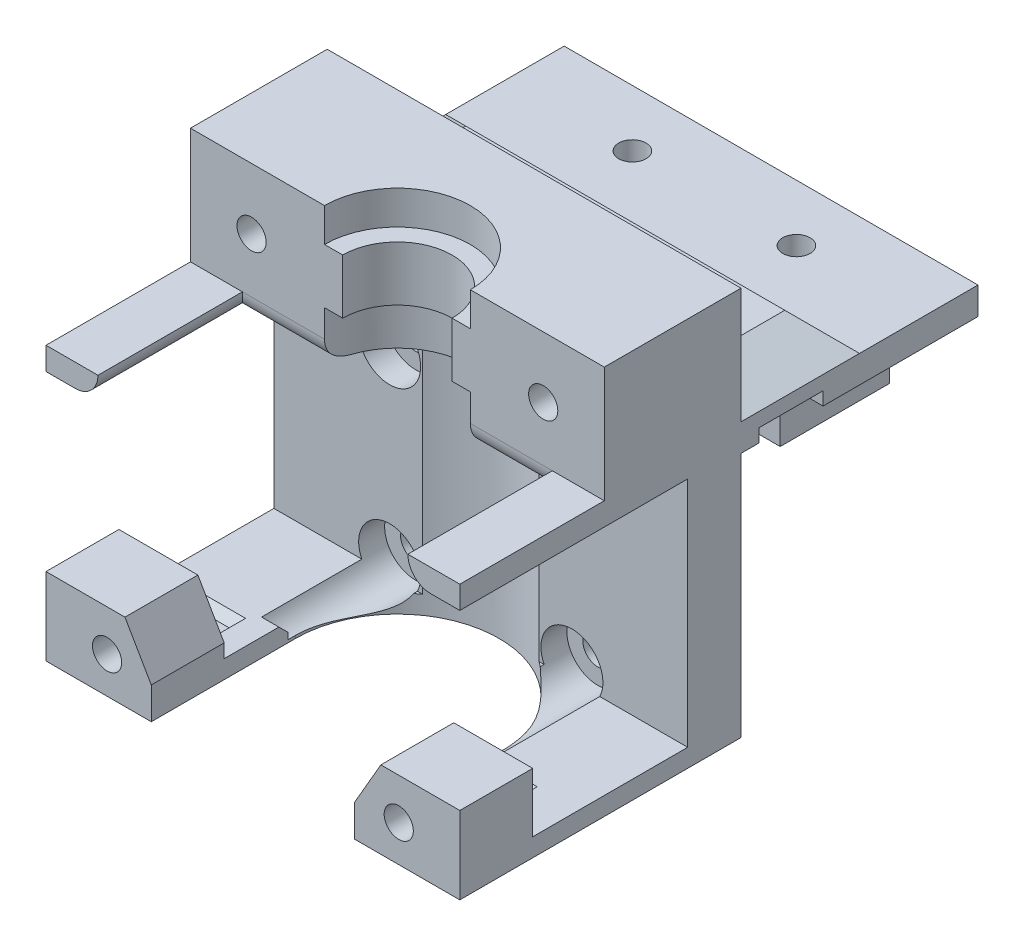
SolidWorks part; units mm, degrees
ref_plane "Front Plane" through (0, 0, 0) normal (0, 0, 1) x (1, 0, 0)
ref_plane "Top Plane" through (0, 0, 0) normal (0, 1, 0) x (1, 0, 0)
ref_plane "Right Plane" through (0, 0, 0) normal (1, 0, 0) x (0, 0, -1)
sketch "Sketch1" plane through (0, 0, 0) normal (0, 0, 1) x (1, 0, 0)
  line L1 (0, 0) -> (45.4, 0)
  line L2 (0, 0) -> (0, 27)
  line L3 (0, 27) -> (45.4, 27)
  line L4 (45.4, 0) -> (45.4, 27)
  dimension "D1" = 45.4
  dimension "D2" = 27
extrude "Boss-Extrude1" add sketch "Sketch1" along normal blind 5.85
sketch "Sketch3" plane through (0, 27, 0) normal (0, 1, 0) x (1, 0, 0)
  line L0 (45.4, 0) -> (0, 0) construction
  line L1 (45.4, 0) -> (0, 0)
  line L2 (45.4, 0) -> (45.4, -5.85)
  line L3 (45.4, -5.85) -> (0, -5.85)
  line L4 (0, 0) -> (0, -5.85)
  line L5 (45.4, -5.85) -> (45.4, 0) construction
  line L6 (45.4, -5.85) -> (0, -5.85) construction
extrude "Boss-Extrude2" add sketch "Sketch3" along normal blind 3
sketch "Sketch4" plane through (0, 0, 5.85) normal (0, 0, 1) x (1, 0, 0)
  line L0 (0, 30) -> (45.4, 30) construction
  line L1 (45.4, 30) -> (0, 30)
  line L2 (45.4, 30) -> (45.4, 27.5)
  line L3 (45.4, 27.5) -> (0, 27.5)
  line L4 (0, 30) -> (0, 27.5)
  line L5 (45.4, 0) -> (45.4, 30) construction
  line L6 (0, 30) -> (0, 0) construction
  dimension "D1" = 2.5
extrude "Boss-Extrude3" add sketch "Sketch4" along normal blind 25
sketch "Sketch6" plane through (0, 0, 5.85) normal (0, 0, 1) x (1, 0, 0)
  line L0 (45.4, 0) -> (45.4, 27.5) construction
  line L1 (0, 0) -> (45.4, 0)
  line L2 (0, 0) -> (0, 2)
  line L3 (0, 2) -> (45.4, 2)
  line L4 (45.4, 0) -> (45.4, 2)
  dimension "D1" = 2
extrude "Boss-Extrude5" add sketch "Sketch6" along normal up to surface (25 mm away) up to face at (22.7, 28.75, 30.85)
sketch "Sketch7" plane through (0, 0, 5.85) normal (0, 0, 1) x (1, 0, 0)
  line L1 (12.7, 23.5) -> (32.7, 23.5) construction
  line L2 (12.7, 23.5) -> (12.7, 3.5) construction
  line L3 (12.7, 3.5) -> (32.7, 3.5) construction
  line L4 (32.7, 23.5) -> (32.7, 3.5) construction
  line L5 (12.7, 23.5) -> (32.7, 3.5) construction
  line L6 (12.7, 3.5) -> (32.7, 23.5) construction
  line L9 (22.7, 2) -> (22.7, 27.5) construction
  line L10 (45.4, 2) -> (0, 2) construction
  line L11 (0, 27.5) -> (45.4, 27.5) construction
  circle A0 centre (12.7, 23.5) radius 1.65
  circle A1 centre (32.7, 23.5) radius 1.65
  circle A2 centre (32.7, 3.5) radius 1.65
  circle A3 centre (12.7, 3.5) radius 1.65
  point P5 (22.7, 13.5)
  dimension "D3" = 3.3
  dimension "D1" = 20
  dimension "D2" = 20
  dimension "D4" = 13.5
extrude "Cut-Extrude1" cut sketch "Sketch7" against normal blind 10
sketch "Sketch8" plane through (0, 0, 5.85) normal (0, 0, 1) x (1, 0, 0)
  circle A0 centre (12.7, 23.5) radius 3.4
  circle A1 centre (32.7, 23.5) radius 3.4
  circle A2 centre (32.7, 3.5) radius 3.4
  circle A3 centre (12.7, 3.5) radius 3.4
  dimension "D1" = 6.8
extrude "Cut-Extrude2" cut sketch "Sketch8" against normal offset from surface 3 and the other way blind 10 up to face at (11.05, 3.5, 0)
sketch "Sketch37" plane through (0, 30, 0) normal (0, 1, 0) x (1, 0, 0)
  line L0 (45.4, 0) -> (0, 0) construction
  line L1 (45.4, -15) -> (0, -15)
  line L2 (45.4, -15) -> (45.4, 0)
  line L3 (45.4, 0) -> (0, 0)
  line L4 (0, -15) -> (0, 0)
  line L5 (22.7, 0) -> (22.7, -15) construction
  line L6 (45.4, 0) -> (0, 0) construction
  line L7 (0, 0) -> (0, -30.85) construction
  dimension "D2" = 15
extrude "Boss-Extrude16" add sketch "Sketch37" along normal blind 12.7
sketch "Sketch9" plane through (0, 2, 0) normal (0, 1, 0) x (1, 0, 0)
  line L1 (22.7, -5.85) -> (22.7, -30.85) construction
  line L3 (0, -30.85) -> (45.4, -30.85) construction
  line L6 (11.55, -15) -> (11.55, -30.85)
  line L7 (11.55, -30.85) -> (33.85, -30.85)
  line L8 (33.85, -15) -> (33.85, -30.85)
  line L9 (11.55, -15) -> (33.85, -30.85) construction
  line L10 (11.55, -30.85) -> (33.85, -15) construction
  arc A1 (33.85, -15) -> (11.55, -15) centre (22.7, -15) ccw
  point P13 (22.7, -22.925)
  dimension "D1" = 11.15
  dimension "D2" = 22.3
extrude "Cut-Extrude3" cut sketch "Sketch9" against normal through all
sketch "Sketch10" plane through (0, 27.5, 0) normal (0, -1, 0) x (1, 0, 0)
  line L1 (14.7, 15) -> (14.7, 30.85)
  line L2 (30.7, 15) -> (30.7, 30.85)
  line L3 (14.7, 30.85) -> (30.7, 30.85)
  line L4 (0, 30.85) -> (45.4, 30.85) construction
  arc A0 (14.7, 15) -> (30.7, 15) centre (22.7, 15) ccw
  dimension "D1" = 16
extrude "Cut-Extrude4" cut sketch "Sketch10" against normal through all
ref_plane "Plane2" through (0, 33, 0) normal (0, 1, 0) x (1, 0, 0)
sketch "Sketch18" plane through (0, 0, 0) normal (0, 0, -1) x (-1, 0, 0)
  line L0 (-45.4, 0) -> (-45.4, 42.7) construction
  line L1 (0, 27) -> (-45.4, 27)
  line L2 (0, 27) -> (0, 30)
  line L3 (0, 30) -> (-45.4, 30)
  line L4 (-45.4, 27) -> (-45.4, 30)
  line L5 (0, 27) -> (-45.4, 30) construction
  line L6 (0, 30) -> (-45.4, 27) construction
  line L7 (0, 42.7) -> (0, 0) construction
  line L11 (0, 0) -> (-45.4, 0) construction
  point P4 (-22.7, 28.5)
  dimension "D1" = 3
  dimension "D2" = 27
extrude "Boss-Extrude8" add sketch "Sketch18" along normal blind 26
sketch "Sketch19" plane through (0, 27, 0) normal (0, -1, 0) x (1, 0, 0)
  line L0 (45.4, -26) -> (0, -26) construction
  line L1 (35.7, -26) -> (9.7, -26)
  line L2 (35.7, -26) -> (35.7, -14)
  line L3 (35.7, -14) -> (9.7, -14)
  line L4 (9.7, -26) -> (9.7, -14)
  line L5 (35.7, -26) -> (9.7, -14) construction
  line L6 (35.7, -14) -> (9.7, -26) construction
  line L7 (22.7, -26) -> (22.7, 0) construction
  line L8 (45.4, -26) -> (0, -26) construction
  line L9 (0, 0) -> (45.4, 0) construction
  point P4 (22.7, -20)
  dimension "D1" = 12
  dimension "D2" = 26
extrude "Boss-Extrude9" add sketch "Sketch19" along normal blind 11.2
sketch "Sketch20" plane through (0, 15.8, 0) normal (0, -1, 0) x (1, 0, 0)
  line L0 (9.7, -26) -> (0, -26) construction
  line L1 (31.698, -19.7827) -> (13.6999, -19.7827) construction
  circle A0 centre (31.698, -19.7827) radius 1.5
  circle A1 centre (13.6999, -19.7827) radius 1.5
  dimension "D1" = 3
  dimension "D2" = 3
  dimension "D3" = 17.9981
  dimension "D5" = 6.2173
extrude "Cut-Extrude9" cut sketch "Sketch20" against normal through all
sketch "Sketch21" plane through (0, 30, 0) normal (0, 1, 0) x (1, 0, 0)
  line L1 (45.4, 0) -> (0, 0)
  line L2 (45.4, 0) -> (45.4, 10)
  line L3 (45.4, 10) -> (0, 10)
  line L4 (0, 0) -> (0, 10)
  line L5 (45.4, 0) -> (0, 10) construction
  line L6 (45.4, 10) -> (0, 0) construction
  line L7 (0, 26) -> (0, 0) construction
  line L8 (45.4, -30.85) -> (45.4, -15) construction
  point P4 (22.7, 5)
  dimension "D1" = 10
extrude "Boss-Extrude10" add sketch "Sketch21" along normal blind 3
sketch "Sketch22" plane through (45.4, 0, 0) normal (1, 0, 0) x (0, 0, -1)
  line L0 (26, 27) -> (0, 27) construction
  line L1 (2, 27) -> (9, 27)
  line L2 (2, 27) -> (2, 28.45)
  line L3 (2, 28.45) -> (9, 28.45)
  line L4 (9, 27) -> (9, 28.45)
  line L5 (2, 27) -> (9, 28.45) construction
  line L6 (2, 28.45) -> (9, 27) construction
  line L8 (0, 0) -> (0, 27) construction
  point P4 (5.5, 27.725)
  dimension "D1" = 1.45
  dimension "D2" = 2
  dimension "D3" = 7
extrude "Cut-Extrude10" cut sketch "Sketch22" against normal through all
sketch "Sketch23" plane through (0, 28.45, 0) normal (0, -1, 0) x (1, 0, 0)
  line L0 (0, -9) -> (45.4, -9) construction
  line L1 (10, -9) -> (13, -9)
  line L2 (10, -9) -> (10, -2)
  line L3 (10, -2) -> (13, -2)
  line L4 (13, -9) -> (13, -2)
  line L5 (10, -9) -> (13, -2) construction
  line L6 (10, -2) -> (13, -9) construction
  line L7 (0, -2) -> (45.4, -2) construction
  line L9 (32.4, -9) -> (35.4, -9)
  line L10 (32.4, -9) -> (32.4, -2)
  line L11 (32.4, -2) -> (35.4, -2)
  line L12 (35.4, -9) -> (35.4, -2)
  line L13 (32.4, -9) -> (35.4, -2) construction
  line L14 (32.4, -2) -> (35.4, -9) construction
  line L15 (0, -9) -> (0, -2) construction
  line L16 (45.4, -9) -> (45.4, -2) construction
  point P4 (11.5, -5.5)
  point P13 (33.9, -5.5)
  dimension "D1" = 3
  dimension "D2" = 3
  dimension "D3" = 10
  dimension "D4" = 10
extrude "Cut-Extrude11" cut sketch "Sketch23" against normal blind 10
sketch "Sketch24" plane through (0, 28.45, 0) normal (0, -1, 0) x (1, 0, 0)
  line L1 (13, -2) -> (32.4, -2)
  line L2 (13, -2) -> (13, -9)
  line L3 (13, -9) -> (32.4, -9)
  line L4 (32.4, -2) -> (32.4, -9)
  line L5 (13, -2) -> (32.4, -9) construction
  line L6 (13, -9) -> (32.4, -2) construction
  point P4 (22.7, -5.5)
extrude "Boss-Extrude11" add sketch "Sketch24" along normal up to surface (1.45 mm away) up to face at (22.7, 27, -18.75)
chamfer "Chamfer1" distance 8 angle 45 2 edges at (32.4, 33, -5.5) (13, 33, -5.5)
chamfer "Chamfer2" distance 3 angle 60 2 edges at (45.4, 33, -5) (0, 33, -5)
chamfer "Chamfer3" distance 3 angle 45 1 edges at (22.7, 30, -10)
chamfer "Chamfer4" distance 2.1 angle 45 2 edges at (9.7, 27, -20) (35.7, 27, -20)
sketch "Sketch35" plane through (0, 0, -26) normal (0, 0, -1) x (-1, 0, 0)
  line L0 (0, 27) -> (0, 30) construction
  line L1 (0, 27) -> (-7.6, 27)
  line L2 (0, 27) -> (0, 28.5)
  line L3 (0, 28.5) -> (-7.6, 28.5)
  line L4 (-7.6, 27) -> (-7.6, 28.5)
  line L5 (0, 27) -> (-7.6, 28.5) construction
  line L6 (0, 28.5) -> (-7.6, 27) construction
  point P4 (-3.8, 27.75)
  point P9 (-7.6, 27)
  dimension "D1" = 1.5
extrude "Cut-Extrude14" cut sketch "Sketch35" against normal up to surface (12 mm away) up to face at (22.7, 22.5667, -14)
fillet "Fillet8" radius 10 1 edges at (7.6, 28.5, -20)
sketch "Sketch36" plane through (0, 27.5, 0) normal (0, -1, 0) x (1, 0, 0)
  circle A0 centre (22.7, 15) radius 11.15
extrude "Cut-Extrude15" cut sketch "Sketch36" along normal up to surface (25.5 mm away) up to face at (7.0663, 2, 17.5167)
sketch "Sketch39" plane through (0, 33, 0) normal (0, 1, 0) x (1, 0, 0)
  circle A0 centre (22.7, -15) radius 8
  circle A1 centre (22.7, -15) radius 6
extrude "Boss-Extrude17" add sketch "Sketch39" along normal blind 6
sketch "Sketch40" plane through (0, 30, 0) normal (0, 1, 0) x (1, 0, 0)
  line L1 (0, -15) -> (45.4, -15)
  line L2 (0, -15) -> (0, -25)
  line L3 (0, -25) -> (45.4, -25)
  line L4 (45.4, -15) -> (45.4, -25)
  line L5 (0, -15) -> (45.4, -25) construction
  line L6 (0, -25) -> (45.4, -15) construction
  line L7 (45.4, -15) -> (45.4, 0) construction
  line L8 (0, -15) -> (14.7, -15) construction
  line L9 (0, 0) -> (0, -15) construction
  point P4 (22.7, -20)
  dimension "D1" = 10
extrude "Cut-Extrude16" cut sketch "Sketch40" along normal through all
sketch "Sketch41" plane through (0, 0, 15) normal (0, 0, 1) x (1, 0, 0)
  line L0 (30.7, 42.7) -> (45.4, 42.7) construction
  line L2 (0, 42.7) -> (0, 30) construction
  line L3 (45.4, 42.7) -> (45.4, 30) construction
  line L4 (0, 42.7) -> (14.7, 42.7) construction
  circle A0 centre (6.7, 36) radius 1.6
  circle A1 centre (38.7, 36) radius 1.6
  dimension "D1" = 3.2
  dimension "D2" = 3.2
  dimension "D3" = 6.7
  dimension "D4" = 6.7
  dimension "D5" = 6.7
  dimension "D6" = 6.7
extrude "Cut-Extrude17" cut sketch "Sketch41" against normal through all
sketch "Sketch42" plane through (0, 0, 0) normal (0, 0, -1) x (-1, 0, 0)
  line L1 (-40.3743, 38.9) -> (-42.0486, 36)
  line L2 (-42.0486, 36) -> (-40.3743, 33.1)
  line L3 (-40.3743, 33.1) -> (-37.0257, 33.1)
  line L4 (-37.0257, 33.1) -> (-35.3514, 36)
  line L5 (-35.3514, 36) -> (-37.0257, 38.9)
  line L6 (-37.0257, 38.9) -> (-40.3743, 38.9)
  line L7 (-8.3743, 38.9) -> (-10.0486, 36)
  line L8 (-10.0486, 36) -> (-8.3743, 33.1)
  line L9 (-8.3743, 33.1) -> (-5.0257, 33.1)
  line L10 (-5.0257, 33.1) -> (-3.3514, 36)
  line L11 (-3.3514, 36) -> (-5.0257, 38.9)
  line L12 (-5.0257, 38.9) -> (-8.3743, 38.9)
  line L14 (-45.4, 42.7) -> (0, 42.7) construction
  circle A0 centre (-38.7, 36) radius 2.9 construction
  circle A1 centre (-6.7, 36) radius 2.9 construction
  dimension "D1" = 5.8
extrude "Cut-Extrude18" cut sketch "Sketch42" against normal blind 4 and the other way blind 18
sketch "Sketch43" plane through (0, 0, 30.85) normal (0, 0, 1) x (1, 0, 0)
  line L1 (0, 2) -> (11.55, 2)
  line L2 (0, 2) -> (0, 8.5)
  line L3 (0, 8.5) -> (11.55, 8.5)
  line L4 (11.55, 2) -> (11.55, 8.5)
  line L5 (0, 2) -> (11.55, 8.5) construction
  line L6 (0, 8.5) -> (11.55, 2) construction
  line L7 (45.4, 2) -> (33.85, 2)
  line L8 (45.4, 2) -> (45.4, 8.5)
  line L9 (45.4, 8.5) -> (33.85, 8.5)
  line L10 (33.85, 2) -> (33.85, 8.5)
  line L11 (45.4, 2) -> (33.85, 8.5) construction
  line L12 (45.4, 8.5) -> (33.85, 2) construction
  point P4 (5.775, 5.25)
  point P10 (39.625, 5.25)
  point P12 (11.55, 2)
  point P14 (33.85, 2)
  dimension "D2" = 6.5
  dimension "D4" = 6.5
extrude "Boss-Extrude18" add sketch "Sketch43" against normal blind 8
sketch "Sketch44" plane through (0, 0, 30.85) normal (0, 0, 1) x (1, 0, 0)
  line L1 (0, 0) -> (0, 8.5) construction
  line L2 (45.4, 8.5) -> (45.4, 0) construction
  line L4 (11.55, 0) -> (0, 0) construction
  line L5 (45.4, 0) -> (33.85, 0) construction
  circle A0 centre (6.7, 4) radius 1.6
  circle A1 centre (38.7, 4) radius 1.6
  dimension "D1" = 3.2
  dimension "D2" = 4
  dimension "D3" = 6.7
  dimension "D4" = 6.7
  dimension "D5" = 4
extrude "Cut-Extrude19" cut sketch "Sketch44" against normal blind 10
sketch "Sketch45" plane through (0, 0, 22.85) normal (0, 0, -1) x (-1, 0, 0)
  line L0 (-45.4, 8.5) -> (-33.85, 8.5) construction
  line L1 (-40.3743, 6.9) -> (-42.0486, 4)
  line L2 (-42.0486, 4) -> (-40.3743, 1.1)
  line L3 (-40.3743, 1.1) -> (-37.0257, 1.1)
  line L4 (-37.0257, 1.1) -> (-35.3514, 4)
  line L5 (-35.3514, 4) -> (-37.0257, 6.9)
  line L6 (-37.0257, 6.9) -> (-40.3743, 6.9)
  line L7 (-8.3743, 6.9) -> (-10.0486, 4)
  line L8 (-10.0486, 4) -> (-8.3743, 1.1)
  line L9 (-8.3743, 1.1) -> (-5.0257, 1.1)
  line L10 (-5.0257, 1.1) -> (-3.3514, 4)
  line L11 (-3.3514, 4) -> (-5.0257, 6.9)
  line L12 (-5.0257, 6.9) -> (-8.3743, 6.9)
  line L13 (-11.55, 8.5) -> (0, 8.5) construction
  circle A0 centre (-38.7, 4) radius 2.9 construction
  circle A1 centre (-6.7, 4) radius 2.9 construction
  dimension "D1" = 5.8
extrude "Cut-Extrude20" cut sketch "Sketch45" against normal blind 4 and the other way blind 4
sketch "Sketch46" plane through (0, 0, 22.85) normal (0, 0, -1) x (-1, 0, 0)
  line L0 (-36.7368, 8.5) -> (-33.85, 3.5)
  line L1 (-45.4, 8.5) -> (-33.85, 8.5) construction
  line L2 (-33.85, 8.5) -> (-33.85, 2) construction
  line L3 (-33.85, 3.5) -> (-33.85, 8.5)
  line L4 (-33.85, 8.5) -> (-36.7368, 8.5)
  line L5 (-35.3514, 4) -> (-37.0257, 6.9) construction
  line L6 (-11.55, 8.5) -> (-8.6632, 8.5)
  line L7 (-11.55, 8.5) -> (0, 8.5) construction
  line L8 (-8.6632, 8.5) -> (-11.55, 3.5)
  line L9 (-11.55, 2) -> (-11.55, 8.5) construction
  line L10 (-11.55, 3.5) -> (-11.55, 8.5)
  line L11 (-8.3743, 6.9) -> (-10.0486, 4) construction
  dimension "D1" = 5
  dimension "D2" = 5
extrude "Cut-Extrude21" cut sketch "Sketch46" against normal through all
sketch "Sketch47" plane through (0, 27.5, 0) normal (0, -1, 0) x (1, 0, 0)
  line L0 (0, 30.85) -> (14.7, 30.85) construction
  line L1 (14.7, 30.85) -> (5.7, 30.85)
  line L2 (14.7, 30.85) -> (14.7, 15)
  line L3 (14.7, 15) -> (5.7, 15)
  line L4 (5.7, 30.85) -> (5.7, 15)
  line L5 (14.7, 30.85) -> (5.7, 15) construction
  line L6 (14.7, 15) -> (5.7, 30.85) construction
  line L7 (8.3, 15) -> (5.1, 15) construction
  line L8 (30.7, 30.85) -> (39.7, 30.85)
  line L9 (30.7, 30.85) -> (30.7, 15)
  line L10 (30.7, 15) -> (39.7, 15)
  line L11 (39.7, 30.85) -> (39.7, 15)
  line L12 (30.7, 30.85) -> (39.7, 15) construction
  line L13 (30.7, 15) -> (39.7, 30.85) construction
  line L14 (40.3, 15) -> (37.1, 15) construction
  point P4 (10.2, 22.925)
  point P11 (35.2, 22.925)
  point P17 (14.7, 30.85)
  dimension "D1" = 9
  dimension "D2" = 9
extrude "Cut-Extrude22" cut sketch "Sketch47" against normal blind 4
fillet "Fillet11" radius 2.5 4 edges at (10.2, 27.5, 15) (35.2, 27.5, 15) (39.7, 27.5, 22.925) (5.7, 27.5, 22.925)
chamfer "Chamfer7" distance 1 angle 45 4 edges at (10.5994, 2, 15.85) (34.8006, 2, 15.85) (38.7, 2, 18.85) (6.7, 2, 18.85)
